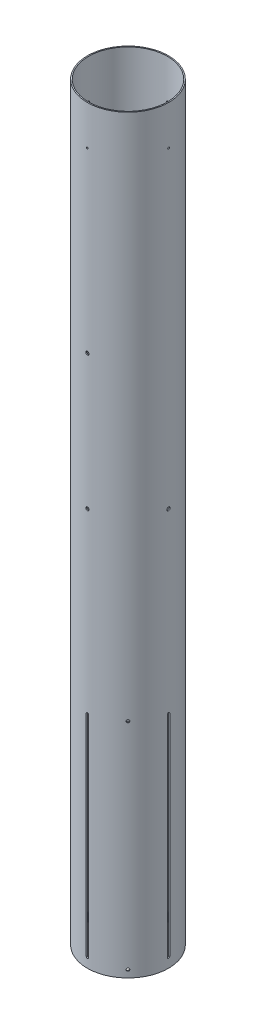
SolidWorks part; units mm, degrees
ref_plane "Front Plane" through (0, 0, 0) normal (0, 0, 1) x (1, 0, 0)
ref_plane "Top Plane" through (0, 0, 0) normal (0, 1, 0) x (1, 0, 0)
ref_plane "Right Plane" through (0, 0, 0) normal (1, 0, 0) x (0, 0, -1)
sketch "Sustainer Tube Profile" plane through (0, 0, 0) normal (0, 1, 0) x (1, 0, 0)
  circle A0 centre (0, 0) radius 76.2
  circle A1 centre (0, 0) radius 78.359
  dimension "D2" = 156.718
extrude "Sustainer Tube Body" add sketch "Sustainer Tube Profile" along normal blind 1447.8
ref_plane "Plane1" through (0, 0, 78.359) normal (0, 0, 1) x (1, 0, 0)
sketch "Fin Slot Profile" plane through (0, 0, 78.359) normal (0, 0, 1) x (1, 0, 0)
  line L0 (0, 0) -> (0, 1447.8) construction
  line L5 (76.2, 1447.8) -> (-76.2, 1447.8) construction
  line L6 (-78.359, 0) -> (78.359, 0) construction
  line L7 (2.3813, 19.05) -> (-2.3813, 19.05)
  line L8 (0, 19.05) -> (0, 425.45)
  line L9 (2.3813, 425.45) -> (-2.3813, 425.45)
  line L10 (-2.3813, 19.05) -> (-2.3813, 425.45)
  line L11 (2.3813, 19.05) -> (2.3813, 425.45)
  arc A0 (-2.3813, 19.05) -> (2.3812, 19.05) centre (0, 19.05) ccw
  arc A1 (2.3813, 425.45) -> (-2.3812, 425.45) centre (0, 425.45) ccw
  dimension "D1" = 406.4
  dimension "D2" = 19.05
  dimension "D3" = 2.3813
extrude "Fin Slot Cut" cut sketch "Fin Slot Profile" against normal up to surface (2.1962 mm away) contours L7 L11 L9 L8 | L10 L7 L8 L9 | L0 L9 A1 | L9 L0 A1 | A0 L0 L7 | L0 A0 L7 region at (-1.1906, 222.25, 78.359) region at (1.0106, 18.0394, 78.359) region at (1.1906, 222.25, 78.359) region at (-1.0106, 18.0394, 78.359) region at (-1.0106, 426.4606, 78.359) region at (1.0106, 426.4606, 78.359) up to face at (0, 1447.8, 76.2)
pattern_circular "Fin Slot Pattern" count 4 over 360 about axis through (0, 1447.8, 0) along (0, 1, 0) of "Fin Slot Cut"
sketch "Sketch1" plane through (0, 0, 0) normal (0, 0, 1) x (1, 0, 0)
  line L0 (76.2, 1447.8) -> (-76.2, 1447.8) construction
  circle A0 centre (0, 1371.6) radius 1.143
  dimension "D1" = 2.286
  dimension "D2" = 76.2
extrude "Cut-Extrude1" [suppressed] cut sketch "Sketch1" against normal through all both and the other way through all
pattern_circular "CirPattern1" [suppressed] count 4 over 360 of bodies 110
sketch "Sketch2" plane through (0, 0, 0) normal (0, 0, 1) x (1, 0, 0)
  line L0 (76.2, 1447.8) -> (-76.2, 1447.8) construction
  circle A0 centre (0, 1028.7) radius 3.175
  dimension "D2" = 419.1
extrude "Vent Hole" cut sketch "Sketch2" against normal through all both and the other way through all
sketch "Sketch3" plane through (0, 0, 0) normal (0, 0, 1) x (1, 0, 0)
  line L0 (78.359, 1447.8) -> (-78.359, 1447.8) construction
  circle A0 centre (0, 768.35) radius 3.175
  dimension "D2" = 6.35
  dimension "D1" = 679.45
extrude "Cut-Extrude3" cut sketch "Sketch3" against normal through all both and the other way through all
pattern_circular "CirPattern2" count 4 over 360 about axis through (0, 1447.8, 0) along (0, 1, 0) of "Cut-Extrude3"
ref_plane "Plane2" through (55.4082, 0, 55.4082) normal (0.7071, 0, 0.7071) x (0, -1, 0)
sketch "Sketch4" plane through (55.4082, 0, 55.4082) normal (0.7071, 0, 0.7071) x (0, -1, 0)
  circle A0 centre (-14.0462, 0) radius 2.5794
  circle A1 centre (-429.4429, 0) radius 2.5794
  dimension "D2" = 14.0462
  dimension "D3" = 429.4429
extrude "Cut-Extrude4" cut sketch "Sketch4" against normal up to surface and the other way through all up to face at (-76.1373, 767.6228, 3.0906)
ref_plane "Plane3" through (0, 0, 0) normal (0.7071, 0, 0.7071) x (0, -1, 0)
sketch "Sketch7" plane through (0, 0, 0) normal (0, -1, 0) x (1, 0, 0)
  line L0 (0, -76.2) -> (0, 76.2) construction
  line L1 (-76.2, 0) -> (76.2, 0) construction
  point P5 (0, 0)
  point P9 (0, 0)
sketch "Sketch8" plane through (0, 0, 0) normal (0, -1, 0) x (1, 0, 0)
  line L0 (0, -76.2) -> (0, 76.2) construction
  line L1 (0, -76.2) -> (0, 76.2) construction
ref_plane "Plane4" through (0, 0, 78.359) normal (0, 0, 1) x (1, 0, 0)
sketch "Sketch9" plane through (0, 0, 78.359) normal (0, 0, 1) x (1, 0, 0)
  line L0 (78.359, 1447.8) -> (-78.359, 1447.8) construction
  point P0 (0, 1371.6)
  dimension "D1" = 76.2
hole_wizard "#4 Clearance Hole1" positions "Sketch9" profile "Sketch10" hole size "#4" standard "ANSI Inch"
sketch "Sketch10" plane through (0, 1371.6, 78.359) normal (1, 0, 0) x (0, -1, 0)
  line L0 (0, 0) -> (0, 5.8066)
  line L1 (0, 5.8066) -> (1.6319, 4.826)
  line L2 (1.6319, 4.826) -> (1.6319, 0)
  line L5 (1.6319, 0) -> (0, 0)
  line L10 (0, 5.8066) -> (-1.6319, 4.826) construction
  line L11 (0, -6.35) -> (0, 107.95) construction
  dimension "Hole Dia." = 3.2639
  dimension "Hole Depth" = 4.826
  dimension "Drill Angle" = 118
pattern_circular "CirPattern3" count 4 every 90 about axis through (0, 1447.8, 0) along (0, 1, 0) of "#4 Clearance Hole1"
equation "\"Length\"= 57"
equation "\"Outer Diameter\"= 6.17"
equation "\"Inner Diameter\"= 6"
equation "\"Wall Thickness\"= 0.085"
equation "\"D1@Sustainer Tube Profile\" = \"Inner Diameter\""
equation "\"D2@Sustainer Tube Profile\" = \"Outer Diameter\""
equation "\"D1@Sustainer Tube Body\" = \"Length\""
equation "\"Root Chord\"= 16"
equation "\"Fin Offset\"= 3 / 4"
equation "\"D1@Fin Slot Profile\"=\"Root Chord\" "
equation "\"D2@Fin Slot Profile\" = \"Fin Offset\""
equation "\"Fin Thickness\"= ( 3 / 16 ) / 2"
equation "\"D3@Fin Slot Profile\"=\"Fin Thickness\""
equation "\"Shear Pin Dia\"= 3 / 32"
equation "\"Shear Pin Offset\"= 3"
equation "\"Bulkhead Screw Dia\"= 1 / 4"
equation "\"Bulkhead Screw Offset\"= 26.75"
equation "\"Rail Button Dia\"= 0.2031"
equation "\"Rail Button Aft Offset\"= 0.553"
equation "\"Rail Button Forward Offset\"= 16.9072"
equation "\"Vent Hole Dia\"= 1 / 4"
equation "\"Vent Hole Offset\"= 16.5"
equation "\"D1@Sketch2\"=\"Vent Hole Dia\""
equation "\"D2@Sketch2\"=\"Vent Hole Offset\""
equation "\"D1@Sketch3\"=\"Bulkhead Screw Offset\""
equation "\"D2@Sketch3\"=\"Bulkhead Screw Dia\""
equation "\"D1@Sketch4\"=\"Rail Button Dia\""
equation "\"D2@Sketch4\"=\"Rail Button Aft Offset\""
equation "\"D3@Sketch4\"=\"Rail Button Forward Offset\""
equation "\"D1@Sketch9\"=\"Shear Pin Offset\""
